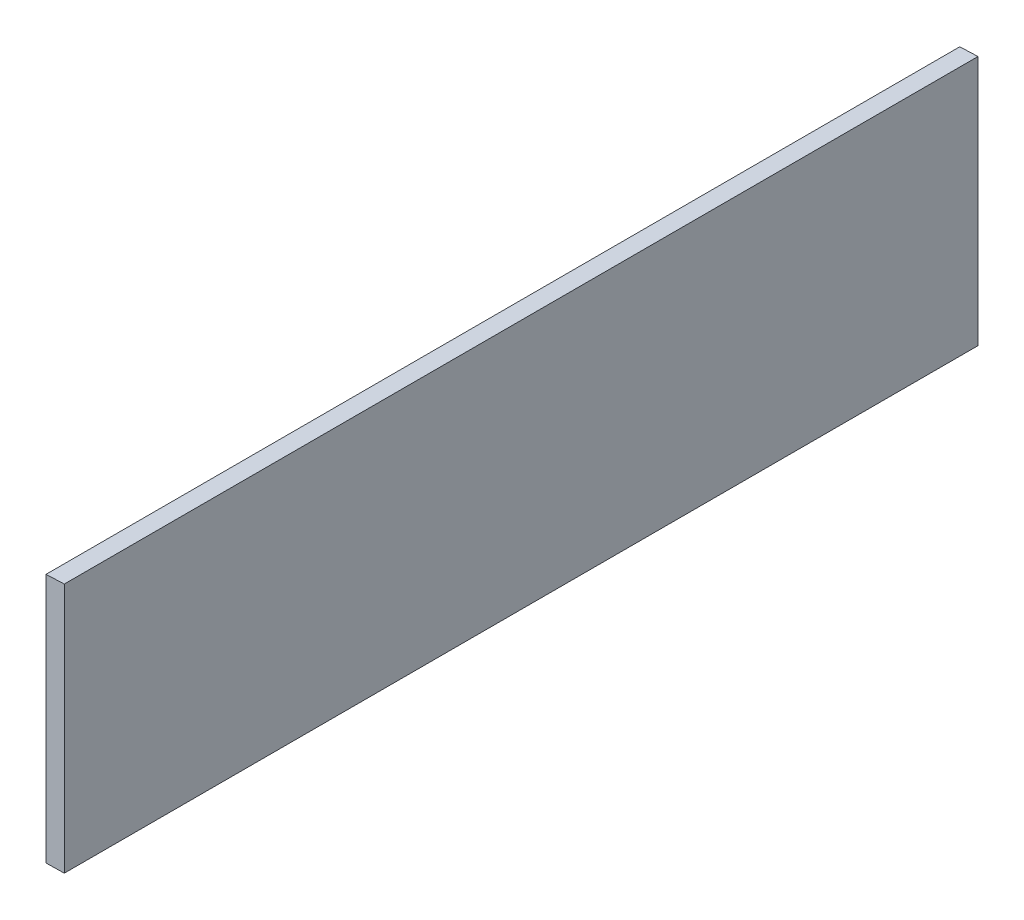
SolidWorks part; units mm, degrees
ref_plane "Front Plane" through (0, 0, 0) normal (0, 0, 1) x (1, 0, 0)
ref_plane "Top Plane" through (0, 0, 0) normal (0, 1, 0) x (1, 0, 0)
ref_plane "Right Plane" through (0, 0, 0) normal (1, 0, 0) x (0, 0, -1)
curve "Curve1"
  spline degree 3 poles (302.6596, 0.1157, 0) (305.3381, -0.0423, 0) (302.669, 0.2207, 0) (300.522, 0.5446, 0) (295.3689, 1.2875, 0) (289.1609, 2.3365, 0) (281.2138, 3.7195, 0) (272.0211, 5.3425, 0) (261.6111, 7.1258, 0) (250.1482, 8.9723, 0) (237.7292, 10.7955, 0) (224.4667, 12.5459, 0) (210.487, 14.2121, 0) (195.9393, 15.7786, 0) (180.9854, 17.2135, 0) (165.7905, 18.4813, 0) (150.5173, 19.555, 0) (135.3259, 20.3976, 0) (120.3737, 20.9834, 0) (105.8119, 21.2902, 0) (91.7835, 21.2891, 0) (78.4214, 20.9725, 0) (65.8465, 20.3288, 0) (54.1674, 19.3419, 0) (43.4744, 18.033, 0) (33.8487, 16.4082, 0) (25.3526, 14.4995, 0) (18.0396, 12.3489, 0) (11.9314, 10.004, 0) (7.0881, 7.5397, 0) (3.4097, 5.063, 0) (1.1505, 2.6895, 0) (-0.3415, 0.4062, 0) (0.6752, -2.0035, 0) (3.5859, -3.0935, 0) (7.5885, -4.3543, 0) (13.2868, -5.2878, 0) (20.4322, -6.0839, 0) (29.0602, -6.6397, 0) (39.0679, -6.9954, 0) (50.3738, -7.1553, 0) (62.8573, -7.1477, 0) (76.3839, -6.9932, 0) (90.8032, -6.6986, 0) (105.9568, -6.2837, 0) (121.6773, -5.7705, 0) (137.79, -5.1759, 0) (154.1149, -4.5178, 0) (170.47, -3.8155, 0) (186.6709, -3.1003, 0) (202.5321, -2.3909, 0) (217.8684, -1.7248, 0) (232.4928, -1.115, 0) (246.2209, -0.6139, 0) (258.8615, -0.2157, 0) (270.2531, 0.0554, 0) (280.189, 0.2196, 0) (288.6505, 0.2748, 0) (295.1556, 0.2617, 0) (300.4646, 0.1437, 0) (302.6596, 0.1157, 0) (305.3381, -0.0423, 0) (302.669, 0.2207, 0) knots -0.014411 -0.006469 -0.001624 0 0.001633 0.006456 0.014273 0.024844 0.037882 0.053108 0.070262 0.089112 0.109474 0.131183 0.154044 0.177808 0.202202 0.22696 0.251816 0.276516 0.300807 0.324444 0.347208 0.368894 0.389314 0.408315 0.425773 0.441588 0.45568 0.468012 0.478567 0.487363 0.494419 0.499795 0.503598 0.50652 0.511061 0.517924 0.527205 0.538874 0.552882 0.569133 0.587486 0.607759 0.629726 0.653145 0.677762 0.703306 0.729491 0.756024 0.782609 0.80895 0.834737 0.859675 0.88346 0.905785 0.926349 0.944858 0.961055 0.974701 0.985589 0.993531 0.998376 1 1.001633 1.006456 1.014273 periodic
sketch "Sketch1" plane through (0, 0, 0) normal (0, 0, 1) x (1, 0, 0)
  line L0 (76.2, 20.8248) -> (76.2, -6.975)
  line L1 (78.232, 20.9058) -> (78.232, -6.9415)
  arc A0 (76.2, -6.975) -> (76.6444, -6.9679) centre (76.2, 6.9185) ccw
  spline S0 degree 3 poles (302.6596, 0.1157) (305.3381, -0.0423) (302.669, 0.2207) (300.522, 0.5446) (295.3689, 1.2875) (289.1609, 2.3365) (281.2138, 3.7195) (272.0211, 5.3425) (261.6111, 7.1258) (250.1482, 8.9723) (237.7292, 10.7955) (224.4667, 12.5459) (210.487, 14.2121) (195.9393, 15.7786) (180.9854, 17.2135) (165.7905, 18.4813) (150.5173, 19.555) (135.3259, 20.3976) (120.3737, 20.9834) (105.8119, 21.2902) (91.7835, 21.2891) (78.4214, 20.9725) (65.8465, 20.3288) (54.1674, 19.3419) (43.4744, 18.033) (33.8487, 16.4082) (25.3526, 14.4995) (18.0396, 12.3489) (11.9314, 10.004) (7.0881, 7.5397) (3.4097, 5.063) (1.1505, 2.6895) (-0.3415, 0.4062) (0.6752, -2.0035) (3.5859, -3.0935) (7.5885, -4.3543) (13.2868, -5.2878) (20.4322, -6.0839) (29.0602, -6.6397) (39.0679, -6.9954) (50.3738, -7.1553) (62.8573, -7.1477) (76.3839, -6.9932) (90.8032, -6.6986) (105.9568, -6.2837) (121.6773, -5.7705) (137.79, -5.1759) (154.1149, -4.5178) (170.47, -3.8155) (186.6709, -3.1003) (202.5321, -2.3909) (217.8684, -1.7248) (232.4928, -1.115) (246.2209, -0.6139) (258.8615, -0.2157) (270.2531, 0.0554) (280.189, 0.2196) (288.6505, 0.2748) (295.1556, 0.2617) (300.4646, 0.1437) (302.6596, 0.1157) (305.3381, -0.0423) (302.669, 0.2207) knots -0.014411 -0.006469 -0.001624 0 0.001633 0.006456 0.014273 0.024844 0.037882 0.053108 0.070262 0.089112 0.109474 0.131183 0.154044 0.177808 0.202202 0.22696 0.251816 0.276516 0.300807 0.324444 0.347208 0.368894 0.389314 0.408315 0.425773 0.441588 0.45568 0.468012 0.478567 0.487363 0.494419 0.499795 0.503598 0.50652 0.511061 0.517924 0.527205 0.538874 0.552882 0.569133 0.587486 0.607759 0.629726 0.653145 0.677762 0.703306 0.729491 0.756024 0.782609 0.80895 0.834737 0.859675 0.88346 0.905785 0.926349 0.944858 0.961055 0.974701 0.985589 0.993531 0.998376 1 1.001633 1.006456 1.014273 only from (304.8, 0) to (304.8, 0) construction
  spline S1 degree 3 poles (302.6596, 0.1157) (305.3381, -0.0423) (302.669, 0.2207) (300.522, 0.5446) (295.3689, 1.2875) (289.1609, 2.3365) (281.2138, 3.7195) (272.0211, 5.3425) (261.6111, 7.1258) (250.1482, 8.9723) (237.7292, 10.7955) (224.4667, 12.5459) (210.487, 14.2121) (195.9393, 15.7786) (180.9854, 17.2135) (165.7905, 18.4813) (150.5173, 19.555) (135.3259, 20.3976) (120.3737, 20.9834) (105.8119, 21.2902) (91.7835, 21.2891) (78.4214, 20.9725) (65.8465, 20.3288) (54.1674, 19.3419) (43.4744, 18.033) (33.8487, 16.4082) (25.3526, 14.4995) (18.0396, 12.3489) (11.9314, 10.004) (7.0881, 7.5397) (3.4097, 5.063) (1.1505, 2.6895) (-0.3415, 0.4062) (0.6752, -2.0035) (3.5859, -3.0935) (7.5885, -4.3543) (13.2868, -5.2878) (20.4322, -6.0839) (29.0602, -6.6397) (39.0679, -6.9954) (50.3738, -7.1553) (62.8573, -7.1477) (76.3839, -6.9932) (90.8032, -6.6986) (105.9568, -6.2837) (121.6773, -5.7705) (137.79, -5.1759) (154.1149, -4.5178) (170.47, -3.8155) (186.6709, -3.1003) (202.5321, -2.3909) (217.8684, -1.7248) (232.4928, -1.115) (246.2209, -0.6139) (258.8615, -0.2157) (270.2531, 0.0554) (280.189, 0.2196) (288.6505, 0.2748) (295.1556, 0.2617) (300.4646, 0.1437) (302.6596, 0.1157) (305.3381, -0.0423) (302.669, 0.2207) knots -0.014411 -0.006469 -0.001624 0 0.001633 0.006456 0.014273 0.024844 0.037882 0.053108 0.070262 0.089112 0.109474 0.131183 0.154044 0.177808 0.202202 0.22696 0.251816 0.276516 0.300807 0.324444 0.347208 0.368894 0.389314 0.408315 0.425773 0.441588 0.45568 0.468012 0.478567 0.487363 0.494419 0.499795 0.503598 0.50652 0.511061 0.517924 0.527205 0.538874 0.552882 0.569133 0.587486 0.607759 0.629726 0.653145 0.677762 0.703306 0.729491 0.756024 0.782609 0.80895 0.834737 0.859675 0.88346 0.905785 0.926349 0.944858 0.961055 0.974701 0.985589 0.993531 0.998376 1 1.001633 1.006456 1.014273 only from (304.8, 0) to (304.8, 0)
  dimension "D1" = 76.2
  dimension "D2" = 2.032
extrude "Boss-Extrude1" add sketch "Sketch1" along normal blind 101.6 contours L1 S1 L0 region at (77.2163, 6.9538, 0)
